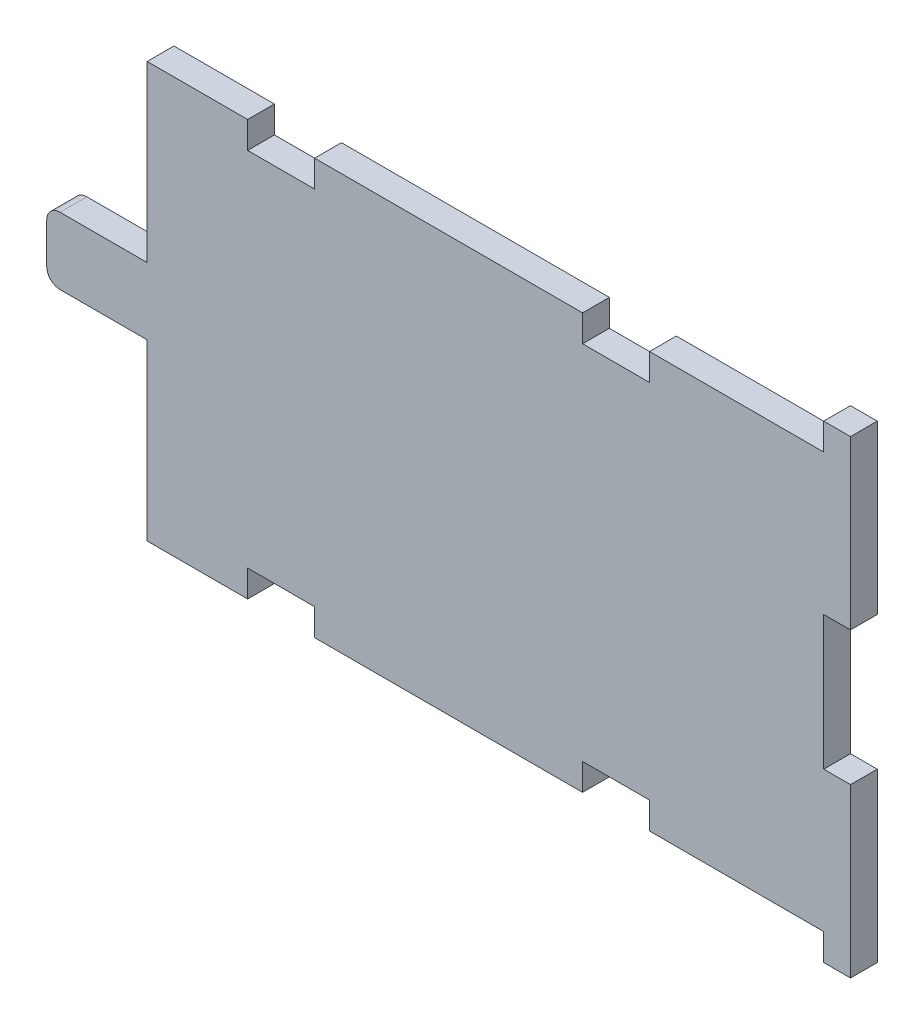
SolidWorks part; units mm, degrees
ref_plane "Front Plane" through (0, 0, 0) normal (0, 0, 1) x (1, 0, 0)
ref_plane "Top Plane" through (0, 0, 0) normal (0, 1, 0) x (1, 0, 0)
ref_plane "Right Plane" through (0, 0, 0) normal (1, 0, 0) x (0, 0, -1)
sketch "Sketch1" plane through (0, 0, 0) normal (0, 0, 1) x (1, 0, 0)
  line L1 (0, 0) -> (101, 0)
  line L2 (0, 0) -> (0, 62)
  line L3 (0, 62) -> (101, 62)
  line L4 (105, 0) -> (105, 62)
  line L6 (105, 0) -> (105, -4)
  line L7 (105, -4) -> (101, -4)
  line L8 (101, 0) -> (101, -4)
  line L10 (105, 62) -> (105, 66)
  line L11 (105, 66) -> (101, 66)
  line L12 (101, 62) -> (101, 66)
  dimension "D1" = 105
  dimension "D2" = 70
  dimension "D3" = 4
  dimension "D4" = 4
  dimension "D5" = 4
  dimension "D6" = 4
extrude "Boss-Extrude1" add sketch "Sketch1" along normal blind 4
sketch "Sketch2" plane through (0, 0, 4) normal (0, 0, 1) x (1, 0, 0)
  line L0 (105, -4) -> (105, 66) construction
  line L1 (105, 41) -> (101, 41)
  line L2 (105, 41) -> (105, 21)
  line L3 (105, 21) -> (101, 21)
  line L4 (101, 41) -> (101, 21)
  line L5 (0, 0) -> (101, 0) construction
  dimension "D1" = 4
  dimension "D2" = 20
  dimension "D3" = 21
extrude "Cut-Extrude1" cut sketch "Sketch2" against normal blind 4
sketch "Sketch3" plane through (0, 0, 4) normal (0, 0, 1) x (1, 0, 0)
  line L0 (0, 31) -> (-20.3898, 31) construction
  line L1 (0, 62) -> (0, 0) construction
  line L3 (-15, 26) -> (0, 26)
  line L4 (-15, 26) -> (-15, 36)
  line L5 (-15, 36) -> (0, 36)
  line L6 (0, 26) -> (0, 36)
  line L7 (-15, 26) -> (0, 36) construction
  line L8 (-15, 36) -> (0, 26) construction
  point P4 (-7.5, 31)
  dimension "D1" = 10
  dimension "D2" = 15
extrude "Boss-Extrude2" add sketch "Sketch3" against normal blind 4
fillet "Fillet1" radius 2 2 edges at (-15, 36, 2) (-15, 26, 2)
sketch "Sketch4" plane through (0, 0, 4) normal (0, 0, 1) x (1, 0, 0)
  line L0 (0, 0) -> (101, 0) construction
  line L1 (15, 0) -> (25, 0)
  line L2 (15, 0) -> (15, 4)
  line L3 (15, 4) -> (25, 4)
  line L4 (25, 0) -> (25, 4)
  line L5 (0, 26) -> (0, 0) construction
  line L6 (65, 0) -> (75, 0)
  line L7 (65, 0) -> (65, 4)
  line L8 (65, 4) -> (75, 4)
  line L9 (75, 0) -> (75, 4)
  line L10 (-15, 31) -> (112.2604, 31) construction
  line L11 (-15, 34) -> (-15, 28) construction
  line L12 (75, 62) -> (75, 58)
  line L13 (65, 58) -> (75, 58)
  line L14 (65, 62) -> (65, 58)
  line L15 (65, 62) -> (75, 62)
  line L16 (25, 62) -> (25, 58)
  line L17 (15, 58) -> (25, 58)
  line L18 (15, 62) -> (15, 58)
  line L19 (15, 62) -> (25, 62)
  dimension "D1" = 10
  dimension "D2" = 10
  dimension "D3" = 15
  dimension "D4" = 40
  dimension "D5" = 4
extrude "Cut-Extrude2" cut sketch "Sketch4" against normal blind 4
